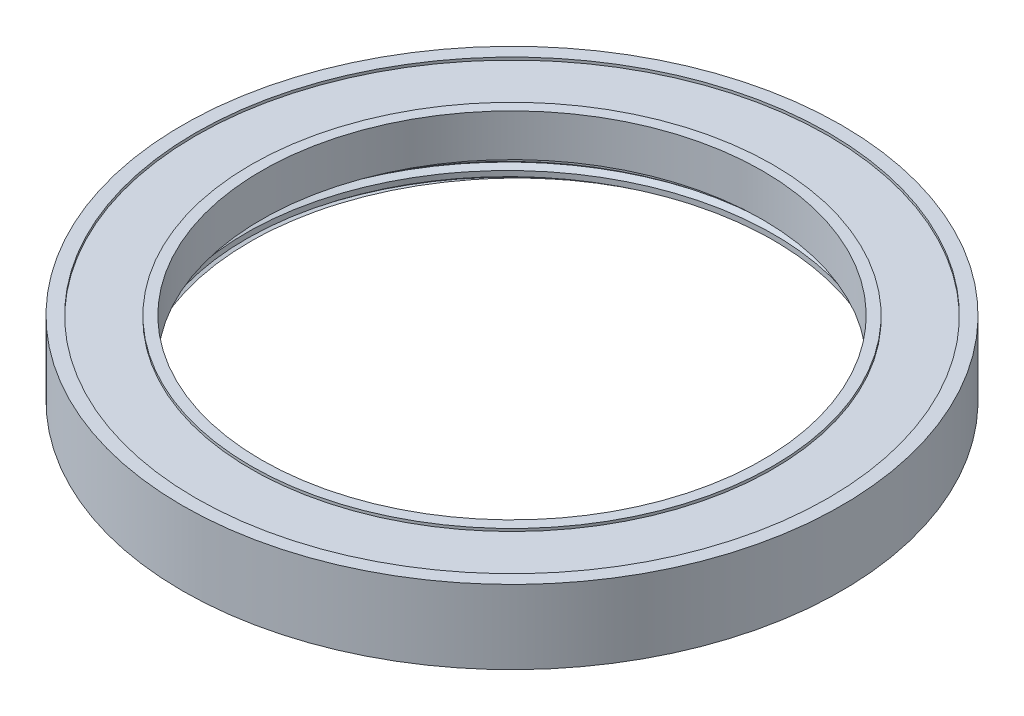
SolidWorks part; units mm, degrees
ref_plane "Front Plane" through (0, 0, 0) normal (0, 0, 1) x (1, 0, 0)
ref_plane "Top Plane" through (0, 0, 0) normal (0, 1, 0) x (1, 0, 0)
ref_plane "Right Plane" through (0, 0, 0) normal (1, 0, 0) x (0, 0, -1)
sketch "Sketch1" plane through (0, 0, 0) normal (1, 0, 0) x (0, 0, -1)
  line L0 (0, 0) -> (0, 62.5288) construction
  line L1 (47.5, 120) -> (47.5, 0)
  line L2 (47.5, 0) -> (62.5, 0)
  line L3 (62.5, 0) -> (62.5, 120)
  line L4 (62.5, 120) -> (47.5, 120)
  line L5 (47.5, 20.15) -> (62.5, 20.15)
  line L6 (62.5, 20.15) -> (62.5, 6.15)
  line L7 (62.5, 6.15) -> (47.5, 6.15)
  line L8 (47.5, 26.3) -> (62.5, 26.3)
  line L9 (47.5, 40.3) -> (62.5, 40.3)
  line L10 (47.5, 46.45) -> (62.5, 46.45)
  line L11 (47.5, 60.45) -> (62.5, 60.45)
  line L12 (47.5, 66.6) -> (62.5, 66.6)
  line L13 (49.5, 120) -> (49.5, 0)
  dimension "D1" = 15
  dimension "D2" = 120
  dimension "D3" = 14
  dimension "D4" = 6.15
  dimension "D5" = 6.15
  dimension "D6" = 14
  dimension "D7" = 6.15
  dimension "D8" = 14
  dimension "D9" = 6.15
  dimension "D10" = 13
  dimension "D11" = 62.5
sketch "Sketch2" plane through (0, 0, 0) normal (1, 0, 0) x (0, 0, -1)
  line L0 (0, 0) -> (0, 62.5288) construction
  line L1 (0, 0) -> (0, 62.5288) construction
  line L2 (47.5, 36.15) -> (47.5, 20.15)
  line L3 (47.5, 20.15) -> (62.5, 20.15)
  line L4 (62.5, 20.15) -> (62.5, 6.15)
  line L5 (62.5, 6.15) -> (47.5, 6.15)
  line L6 (47.5, 6.15) -> (47.5, 20.15)
  line L7 (47.5, 13.15) -> (62.5, 13.15) construction
  line L10 (49.5, 6.65) -> (60, 6.65)
  line L11 (47.5, 36.15) -> (49.5, 36.15)
  line L12 (49.5, 36.15) -> (49.5, 20.15)
  line L13 (49.5, -9.85) -> (60, -9.85)
  line L14 (47.5, 6.15) -> (50, 6.15)
  line L15 (47.5, 6.15) -> (47.5, 12.15)
  line L16 (47.5, 12.15) -> (50, 12.15)
  line L17 (50, 6.15) -> (50, 12.15)
  line L18 (49.5, 36.15) -> (60, 36.15)
  line L19 (49.5, 36.15) -> (49.5, 19.65)
  line L20 (49.5, 19.65) -> (60, 19.65)
  line L21 (60, 36.15) -> (60, 19.65)
  line L22 (49.5, -9.85) -> (49.5, 6.15)
  line L23 (60, -9.85) -> (60, 6.65)
  dimension "D1" = 16
  dimension "D2" = 6
  dimension "D3" = 10.5
  dimension "D4" = 0.5
  dimension "D5" = 60
revolve "Revolve1" add sketch "Sketch2" angle 360 about L1
thread "Thread1" pitch 2 start angle 0, offset 0, length 6, pitch 2.5, diameter 100
ref_plane "Plane1" through (50, 6.65, 0) normal (0, 0, -1) x (1, 0, 0)
sketch "Thread Profile1" plane through (50, 6.65, 0) normal (0, 0, -1) x (1, 0, 0)
  line L0 (0, 0) -> (0, 2) construction
  line L1 (0, 0) -> (1.0825, 0.625)
  line L2 (1.0825, 0.625) -> (1.0825, 0.875)
  line L3 (1.0825, 0.875) -> (0, 1.5)
  line L4 (1.0825, 0.75) -> (0, 0.75) construction
  line L11 (0, 0) -> (0, 1.5)
  point P2 (0, 0)
  dimension "Pitch" = 2
  dimension "Profile_Angle" = 60
  dimension "Profile_Land" = 0.25
  dimension "Profile_Height" = 1.0825
thread "Thread2" pitch 2 profile "Thread Profile2" start angle 0, offset 0, length 4, pitch 2.5, diameter 99
ref_plane "Plane2" through (-49.5, 36.15, 0) normal (0, 0, 1) x (-1, 0, 0)
sketch "Thread Profile2" plane through (-49.5, 36.15, 0) normal (0, 0, 1) x (-1, 0, 0)
  line L0 (0, 0) -> (0, 2) construction
  line L1 (0, 0) -> (1.0825, 0.625)
  line L2 (1.0825, 0.625) -> (1.0825, 0.875)
  line L3 (1.0825, 0.875) -> (0, 1.5)
  line L4 (1.0825, 0.75) -> (0, 0.75) construction
  line L11 (0, 0) -> (0, 1.5)
  point P2 (0, 0)
  dimension "Pitch" = 2
  dimension "Profile_Angle" = 60
  dimension "Profile_Land" = 0.25
  dimension "Profile_Height" = 1.0825
sketch "Sketch3" plane through (0, 0, 0) normal (0, 0, 1) x (1, 0, 0)
  line L0 (49.5, 19.65) -> (-49.5, 19.65) construction
  line L1 (47.5, 36.15) -> (-47.5, 36.15) construction
  line L2 (49.5, 19.65) -> (-49.5, 19.65)
  line L3 (47.5, 36.15) -> (-47.5, 36.15)
  line L4 (0, 19.65) -> (0, 34.025) construction
  line L6 (7.5, 21.8375) -> (-7.5, 21.8375)
  line L7 (7.5, 21.8375) -> (7.5, 31.8375)
  line L8 (7.5, 31.8375) -> (-7.5, 31.8375)
  line L9 (-7.5, 21.8375) -> (-7.5, 31.8375)
  line L10 (7.5, 21.8375) -> (-7.5, 31.8375) construction
  line L11 (7.5, 31.8375) -> (-7.5, 21.8375) construction
  spline S0 degree 2 poles (-48.7941, 30.587) (49.5, 26.3604) (49.5, 30.9) (49.5, 31.025) (40.0463, 31.15) (30.5927, 31.275) (15.2963, 31.4) (0, 31.525) (-15.2963, 31.65) (-30.5927, 31.775) (-40.0463, 31.9) (-49.5, 32.025) (-49.5, 32.15) (-49.5, 32.275) (-40.0463, 32.4) (-30.5927, 32.525) (-15.2963, 32.65) (0, 32.775) (15.2963, 32.9) (30.5927, 33.025) (40.0463, 33.15) (49.5, 33.275) (49.5, 33.4) (49.5, 33.525) (40.0463, 33.65) (30.5927, 33.775) (15.2963, 33.9) (0, 34.025) (-15.2963, 34.15) (-30.5927, 34.275) (-40.0463, 34.4) (-474.8491, 40.1491) (35.8128, 34.7001) knots -0.615504 -0.615504 -0.615504 0.05 0.05 0.1 0.1 0.15 0.15 0.2 0.2 0.25 0.25 0.3 0.3 0.35 0.35 0.4 0.4 0.45 0.45 0.5 0.5 0.55 0.55 0.6 0.6 0.65 0.65 0.7 0.7 0.75 0.75 1.468166 1.468166 1.468166 weights 17.038575 0.348559 1 0.951057 1 0.951057 1 0.951057 1 0.951057 1 0.951057 1 0.951057 1 0.951057 1 0.951057 1 0.951057 1 0.951057 1 0.951057 1 0.951057 1 0.951057 1 0.951057 1 0.297009 19.788609 only from (40.0463, 30.65) to (-49.5, 34.65) construction
  spline S1 degree 2 poles (40.0463, 30.65) (49.5, 30.775) (49.5, 30.9) (49.5, 31.025) (40.0463, 31.15) (30.5927, 31.275) (15.2963, 31.4) (0, 31.525) (-15.2963, 31.65) (-30.5927, 31.775) (-40.0463, 31.9) (-49.5, 32.025) (-49.5, 32.15) (-49.5, 32.275) (-40.0463, 32.4) (-30.5927, 32.525) (-15.2963, 32.65) (0, 32.775) (15.2963, 32.9) (30.5927, 33.025) (40.0463, 33.15) (49.5, 33.275) (49.5, 33.4) (49.5, 33.525) (40.0463, 33.65) (30.5927, 33.775) (15.2963, 33.9) (0, 34.025) (-15.2963, 34.15) (-30.5927, 34.275) (-40.0463, 34.4) (-49.5, 34.525) (-49.5, 34.65) knots 0 0 0 0.05 0.05 0.1 0.1 0.15 0.15 0.2 0.2 0.25 0.25 0.3 0.3 0.35 0.35 0.4 0.4 0.45 0.45 0.5 0.5 0.55 0.55 0.6 0.6 0.65 0.65 0.7 0.7 0.75 0.75 0.8 0.8 0.8 weights 1 0.951057 1 0.951057 1 0.951057 1 0.951057 1 0.951057 1 0.951057 1 0.951057 1 0.951057 1 0.951057 1 0.951057 1 0.951057 1 0.951057 1 0.951057 1 0.951057 1 0.951057 1 0.951057 1
  point P9 (0, 26.8375)
  dimension "D1" = 15
  dimension "D2" = 10
extrude "Cut-Extrude1" cut sketch "Sketch3" against normal through all contours L9 L6 L7 L8
sketch "Sketch4" plane through (0, 0, 0) normal (1, 0, 0) x (0, 0, -1)
  line L0 (62.5, 20.15) -> (-62.5, 20.15) construction
  line L1 (62.5, 20.15) -> (-62.5, 20.15)
  line L3 (-62.5, 20.15) -> (62.5, 20.15)
  line L4 (-62.5, 20.15) -> (-62.5, 40.1698)
  line L5 (-62.5, 40.1698) -> (62.5, 40.1698)
  line L6 (62.5, 20.15) -> (62.5, 40.1698)
extrude "Cut-Extrude2" cut sketch "Sketch4" against normal through all both and the other way through all contours L1 L6 L5 L4
